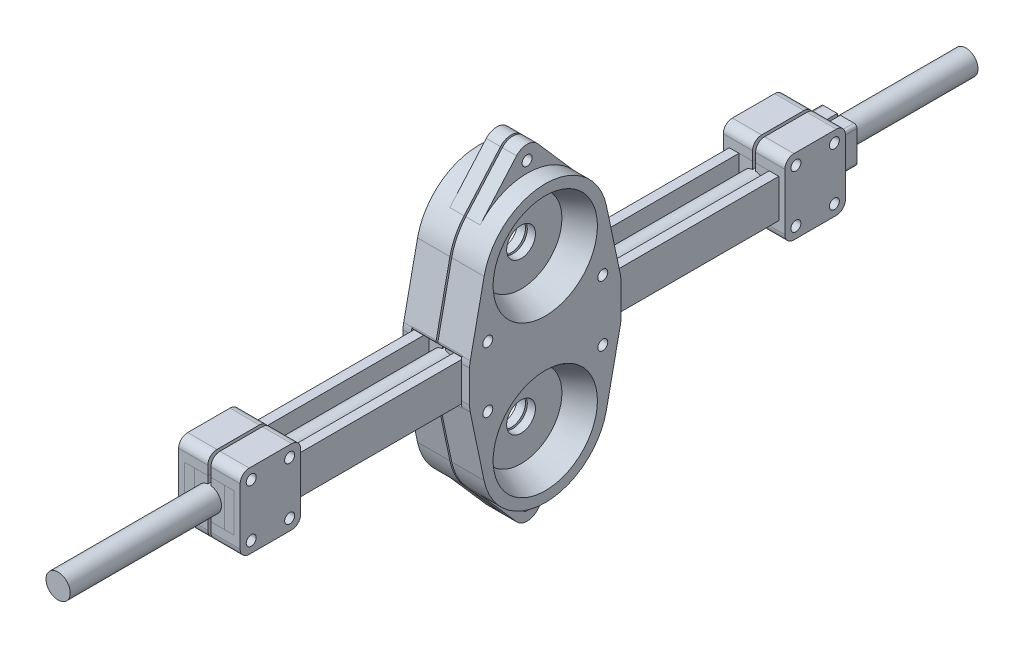
SolidWorks part; units mm, degrees
ref_plane "Front Plane" through (0, 0, 0) normal (0, 0, 1) x (1, 0, 0)
ref_plane "Top Plane" through (0, 0, 0) normal (0, 1, 0) x (1, 0, 0)
ref_plane "Right Plane" through (0, 0, 0) normal (1, 0, 0) x (0, 0, -1)
sketch "Sketch1" plane through (0, 0, 0) normal (0, 0, 1) x (1, 0, 0)
  line L0 (0, 0) -> (0, 67.0118) construction
  line L1 (-6.5875, 0) -> (6.5875, 0) construction
  line L2 (8.175, -6.35) -> (5, -6.35)
  line L3 (-8.175, 6.35) -> (-5, 6.35)
  line L4 (-8.175, 6.35) -> (-8.175, -6.35)
  line L5 (-8.175, -6.35) -> (-5, -6.35)
  line L6 (-5, 6.35) -> (-5, -6.35)
  line L7 (-8.175, 6.35) -> (-5, -6.35) construction
  line L8 (-8.175, -6.35) -> (-5, 6.35) construction
  line L9 (5, 6.35) -> (5, -6.35)
  line L10 (8.175, 6.35) -> (5, 6.35)
  line L11 (8.175, 6.35) -> (8.175, -6.35)
  circle A0 centre (0, 0) radius 4
  dimension "D1" = 8
  dimension "D2" = 12.7
  dimension "D3" = 3.175
  dimension "D4" = 1
extrude "Boss-Extrude1" add sketch "Sketch1" along normal mid plane 200 contours L11 L10 L9 L2 | L6 L3 L4 L5 region at (6.5875, 0, 0) region at (-6.5875, 0, 0)
extrude "Boss-Extrude2" add sketch "Sketch1<3>" along normal mid plane 300 separate body contours A0
sketch "Sketch1<3>" plane through (0, 0, 0) normal (0, 0, 1) x (1, 0, 0) same geometry as "Sketch1"
sketch "Sketch2" plane through (0, 0, 100) normal (0, 0, 1) x (1, 0, 0)
  line L0 (0, 0) -> (0, 8.6431) construction
  line L1 (5, 6.35) -> (5, -6.35)
  line L2 (5, -6.35) -> (0.5, -6.35)
  line L3 (0.5, -6.35) -> (0.5, -3.9686)
  line L4 (0.5, 3.9686) -> (0.5, 6.35)
  line L5 (0.5, 6.35) -> (5, 6.35)
  circle A0 centre (0, 0) radius 4 construction
  circle A1 centre (0, 0) radius 4
  line M3 (5, 6.35) -> (5, -6.35)
  dimension "D1" = 0.5
extrude "Boss-Extrude3" add sketch "Sketch2" against normal blind 20 separate body contours A1 L3 L2 L5 L4 M3 region at (4.8653, 0, 100)
sketch "Sketch4" plane through (0, 0, 100) normal (0, 0, 1) x (1, 0, 0)
  line L0 (0.5, 6.35) -> (8.175, 6.35)
  line L1 (8.175, 6.35) -> (8.175, -6.35)
  line L2 (8.175, -6.35) -> (0.5, -6.35)
  line L3 (8.175, 6.35) -> (8.175, -6.35) construction
  line L4 (0.5, 6.35) -> (0.5, 12.35)
  line L5 (0.5, 12.35) -> (10.175, 12.35)
  line L6 (10.175, 12.35) -> (10.175, -12.35)
  line L7 (10.175, -12.35) -> (0.5, -12.35)
  line L8 (0.5, -12.35) -> (0.5, -6.35)
  dimension "D1" = 6
  dimension "D2" = 2
extrude "Boss-Extrude4" add sketch "Sketch4" against normal up to surface (20 mm away) separate body up to face at (2.5833, 0, 80)
sketch "Sketch5" plane through (0.5, 0, 0) normal (-1, 0, 0) x (0, 0, 1)
  line L0 (80, 11.0312) -> (100, 6.35) construction
  line L5 (80, 6.35) -> (80, 12.35) construction
  line L6 (96.35, 8.6906) -> (83.65, 8.6906) construction
  circle A0 centre (96.35, 8.6906) radius 1.65
  circle A1 centre (83.65, 8.6906) radius 1.65
  point P8 (90, 8.6906)
  dimension "D1" = 3.3
  dimension "D2" = 2
extrude "Cut-Extrude1" cut sketch "Sketch5" against normal through all
mirror "Mirror1" about plane through (0, 0, 0) normal (0, 1, 0) of "Cut-Extrude1"
fillet "Fillet1" radius 3 4 edges at (5.3375, -12.35, 80) (5.3375, -12.35, 100) (5.3375, 12.35, 80) (5.3375, 12.35, 100)
mirror "Mirror2" about plane through (0, 0, 0) normal (1, 0, 0) of bodies 107 110
mirror "Mirror5" about plane through (0, 0, 0) normal (0, 0, 1) of bodies 110 112 107 111
extrude "Boss-Extrude5" add sketch "Sketch2<3>" along normal mid plane 45 from surface separate body contours A1 L3 L2 L5 L4 M3 region at (4.8653, 0, 100) starting at plane "Front Plane"
sketch "Sketch2<3>" plane through (0, 0, 100) normal (0, 0, 1) x (1, 0, 0) same geometry as "Sketch2"
mirror "Mirror4" about plane through (0, 0, 0) normal (1, 0, 0) of bodies 113
sketch "Sketch6" plane through (0, 0, 0) normal (1, 0, 0) x (0, 0, -1)
  line L0 (0, 25) -> (0, -25) construction
  line L2 (-20.2122, 29.2296) -> (-25, 6.35)
  line L3 (-100, 6.35) -> (100, 6.35) construction
  line L4 (20.2122, 29.2296) -> (25, 6.35)
  line L5 (-25, 6.35) -> (25, 6.35)
  line L6 (0, 0) -> (23.5352, 0) construction
  line L7 (-20.2122, -29.2296) -> (-25, -6.35)
  line L8 (20.2122, -29.2296) -> (25, -6.35)
  line L9 (-25, -6.35) -> (25, -6.35)
  line L10 (-25, -6.35) -> (-25, 6.35)
  line L11 (25, 6.35) -> (25, -6.35)
  line L12 (-3.4998, 52.3617) -> (-15.5419, 38.5967)
  line L13 (3.4998, 52.3617) -> (15.5419, 38.5967)
  line L14 (0, 49.3) -> (0, 25) construction
  line L15 (-3.4998, -52.3617) -> (-15.5419, -38.5967)
  line L16 (3.4998, -52.3617) -> (15.5419, -38.5967)
  circle A0 centre (0, 25) radius 4.7625
  circle A1 centre (0, -25) radius 4.7625
  circle A2 centre (0, 25) radius 13.5
  circle A3 centre (0, -25) radius 13.5
  circle A4 centre (0, 25) radius 20.65 construction
  arc A5 (-20.2122, 29.2296) -> (20.2122, 29.2296) centre (0, 25) cw
  arc A6 (-20.2122, -29.2296) -> (20.2122, -29.2296) centre (0, -25) ccw
  circle A7 centre (0, 49.3) radius 1.65
  arc A8 (3.4998, 52.3617) -> (-3.4998, 52.3617) centre (0, 49.3) ccw
  circle A9 centre (0, -49.3) radius 1.65
  arc A10 (3.4998, -52.3617) -> (-3.4998, -52.3617) centre (0, -49.3) cw
  point P24 (0, 6.35)
  dimension "D1" = 9.525
  dimension "D3" = 27
  dimension "D5" = 2
  dimension "D6" = 3.3
  dimension "D7" = 3
  dimension "D8" = 2
  dimension "D2" = 50
  dimension "D4" = 50
extrude "Boss-Extrude6" add sketch "Sketch6" against normal mid plane 6 separate body contours A2 A0 | A3 A1 region at (0, 25, 13.1182) region at (0, -25, 13.1182)
extrude "Boss-Extrude7" add sketch "Sketch6<3>" along normal mid plane 22 contours A5 L2 L5 L4 A2 | L7 A6 L8 L9 A3 | L11 L5 L10 L9 region at (0, 33.9302, 17.9113) region at (0, 0, 0) region at (0, -6.986, 0)
sketch "Sketch6<3>" plane through (0, 0, 0) normal (1, 0, 0) x (0, 0, -1) same geometry as "Sketch6"
extrude "Cut-Extrude2" cut sketch "Sketch6<4>" against normal mid plane 16.5 contours L11 L5 L10 L9 region at (0, 0, 0)
sketch "Sketch6<4>" plane through (0, 0, 0) normal (1, 0, 0) x (0, 0, -1) same geometry as "Sketch6"
draft "Draft1" type of draft neutral plane draft angle 25 faces to draft 2 face at (3, 25, -13.5) face at (3, -25, -13.5) neutral plane through (3, 0, 0) neutral plane normal (1, 0, 0) parameters "D1"=25
draft "Draft2" type of draft neutral plane draft angle 25 faces to draft 2 face at (-11, 25, -13.5) face at (-11, -25, -13.5) neutral plane through (-3, 0, 0) neutral plane normal (-1, 0, 0) parameters "D1"=25
sketch "Sketch7" plane through (11, 0, 0) normal (1, 0, 0) x (0, 0, -1)
  line L1 (-19, -10) -> (19, -10) construction
  line L2 (-19, -10) -> (-19, 10) construction
  line L3 (-19, 10) -> (19, 10) construction
  line L4 (19, -10) -> (19, 10) construction
  line L5 (-19, -10) -> (19, 10) construction
  line L6 (-19, 10) -> (19, -10) construction
  line L10 (-100, 6.35) -> (100, 6.35) construction
  circle A0 centre (-19, 10) radius 1.65
  circle A1 centre (19, 10) radius 1.65
  circle A2 centre (-19, -10) radius 1.65
  circle A3 centre (19, -10) radius 1.65
  point P0 (0, 0)
  dimension "D1" = 3.3
  dimension "D2" = 2
  dimension "D3" = 38
extrude "Cut-Extrude3" cut sketch "Sketch7" against normal through all
extrude "Boss-Extrude9" add sketch "Sketch6<5>" along normal mid plane 10 contours L13 A8 L12 A5 A7 | A10 L16 A6 L15 A9 region at (0, 45.2509, 9.2599) region at (0, -45.9967, 0)
sketch "Sketch6<5>" plane through (0, 0, 0) normal (1, 0, 0) x (0, 0, -1) same geometry as "Sketch6"
fillet "Fillet2" radius 1 4 edges at (0, 6.35, 25) (0, -6.35, 25) (0, -6.35, -25) (0, 6.35, -25) tangent propagation no
fillet "Fillet3" radius 10 8 edges at (9.625, -6.35, 25) (9.625, 6.35, 25) (9.625, 6.35, -25) (9.625, -6.35, -25) (-9.625, -6.35, -25) (-9.625, 6.35, -25) (-9.625, -6.35, 25) (-9.625, 6.35, 25)
sketch "Sketch8" plane through (0, 0, 0) normal (1, 0, 0) x (0, 0, -1)
  line L1 (-64.7265, 73.8253) -> (42.9221, 73.8253)
  line L2 (-64.7265, 73.8253) -> (-64.7265, -72.7768)
  line L3 (-64.7265, -72.7768) -> (42.9221, -72.7768)
  line L4 (42.9221, 73.8253) -> (42.9221, -72.7768)
extrude "Cut-Extrude4" cut sketch "Sketch8" against normal mid plane 0.6
sketch "Sketch9" plane through (0, 0, -100) normal (0, 0, -1) x (-1, 0, 0)
  line L0 (-0.5, 6) -> (-0.5, -6)
  line L1 (-6, -6) -> (6, -6)
  line L2 (-6, -6) -> (-6, 6)
  line L3 (-6, 6) -> (6, 6)
  line L4 (6, -6) -> (6, 6)
  line L5 (-6, -6) -> (6, 6) construction
  line L6 (-6, 6) -> (6, -6) construction
  line L7 (-0.5, 3.9686) -> (-0.5, 6.35) construction
  line L8 (0.5, 6) -> (0.5, -6)
  line L9 (0.5, 3.9686) -> (0.5, 6.35) construction
  circle A0 centre (0, 0) radius 4 construction
  circle A1 centre (0, 0) radius 4
  point P0 (0, 0)
  arc M5 (-0.5, -3.9686) -> (-0.5, 3.9686) centre (0, 0) cw
  line M6 (-0.5, 3.9686) -> (-0.5, 6.35)
  line M8 (-5, 6.35) -> (-5, -6.35)
  line M10 (-0.5, -6.35) -> (-0.5, -3.9686)
  dimension "D1" = 12
extrude "Boss-Extrude10" add sketch "Sketch9" along normal blind 8 contours L3 L1 M8 M10 M5 M6 | L3 L2 L1 M8 | A1 L8 L1 L4 L3 region at (0.6282, 4.9843, -100) region at (-3.25, 5.868, -100) region at (5.5, 0, -100)
fillet "Fillet4" radius 1 2 edges at (6, -6, -104) (6, 6, -104)
fillet "Fillet5" radius 1 2 edges at (-6, -6, -104) (-6, 6, -104)
